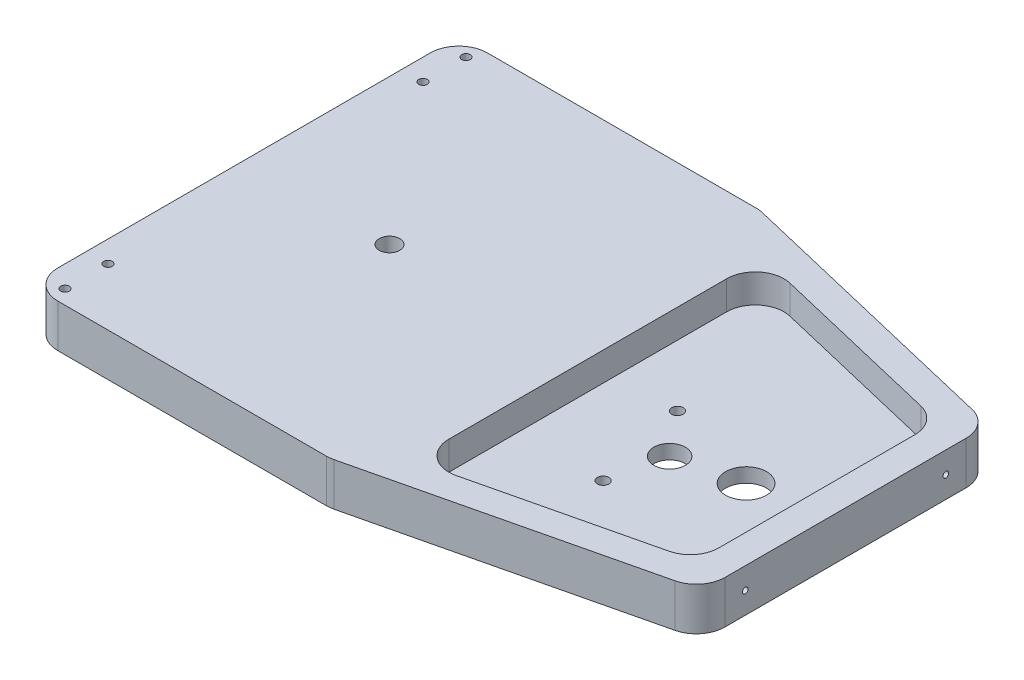
SolidWorks part; units mm, degrees
material "Carvalho"
ref_plane "Plano frontal" through (0, 0, 0) normal (0, 0, 1) x (1, 0, 0)
ref_plane "Plano superior" through (0, 0, 0) normal (0, 1, 0) x (1, 0, 0)
ref_plane "Plano direito" through (0, 0, 0) normal (1, 0, 0) x (0, 0, -1)
sketch "Esboço1" plane through (0, 0, 0) normal (0, 1, 0) x (1, 0, 0)
  line L0 (210, 50) -> (105, 75)
  line L1 (0, -75) -> (105, -75)
  line L2 (0, -75) -> (0, 75)
  line L3 (0, 75) -> (105, 75)
  line L4 (210, -50) -> (210, 50)
  line L7 (105, -75) -> (210, -50)
  line L8 (-14.8259, 0) -> (14.392, 0) construction
  line L9 (0, 21.2472) -> (0, -16.7598) construction
  circle A0 centre (50.8, 0) radius 3.5719
  circle A1 centre (175.26, 0) radius 7.14
  circle A2 centre (153.7069, -5.1317) radius 5.5
  circle A3 centre (153.7069, -5.1317) radius 4.5 construction
  circle A4 centre (7.5, -70) radius 1.5
  circle A5 centre (7.5, -55) radius 1.5
  circle A6 centre (7.5, -70) radius 1.5 construction
  circle A7 centre (7.5, -55) radius 1.5 construction
  circle A8 centre (7.5, 55) radius 1.5
  circle A9 centre (7.5, 70) radius 1.5
  point P0 (0, 0)
  dimension "D3" = 7.1437
  dimension "D5" = 14.28
  dimension "D9" = 1
  dimension "D1" = 25
  dimension "D2" = 150
  dimension "D4" = 50.8
  dimension "D6" = 210
  dimension "D7" = 175.26
  dimension "D8" = 105
extrude "Ressalto-extrusão1" add sketch "Esboço1" along normal blind 15
sketch "Esboço2" plane through (210, 0, 0) normal (1, 0, 0) x (0, 0, -1)
  line L0 (0, 15) -> (0, 0) construction
  line L1 (-50, 15) -> (50, 15) construction
  circle A0 centre (35, 7.5) radius 1
  circle A1 centre (-35, 7.5) radius 1
  point P9 (0, 7.5)
  dimension "D1" = 2
  dimension "D2" = 35
extrude "Corte-extrusão1" cut sketch "Esboço2" against normal blind 10
sketch "Esboço3" plane through (0, 15, 0) normal (0, 1, 0) x (1, 0, 0)
  line L0 (200, 42.1014) -> (200, -42.1014)
  line L1 (200, -42.1014) -> (120, -61.149)
  line L2 (120, -61.149) -> (120, 61.149)
  line L3 (120, 61.149) -> (200, 42.1014)
  line L4 (210, 50) -> (105, 75) construction
  line L5 (105, -75) -> (210, -50) construction
  line L6 (210, -50) -> (210, 50) construction
  line L7 (0, 75) -> (0, -75) construction
  line L8 (-22.821, 0) -> (224.4652, 0) construction
  dimension "D1" = 10
  dimension "D2" = 120
  dimension "D3" = 10
extrude "Corte-extrusão2" cut sketch "Esboço3" against normal blind 10
fillet "Filete1" radius 10 10 edges at (105, 7.5, 75) (0, 7.5, 75) (0, 7.5, -75) (210, 7.5, 50) (105, 7.5, -75) (210, 7.5, -50) (120, 10, 61.149) (200, 10, 42.1014) (200, 10, -42.1014) (120, 10, -61.149)
sketch "Esboço5" plane through (0, 0, 0) normal (0, -1, 0) x (1, 0, 0)
  line L0 (175.26, 0) -> (111.2499, 15.2405) construction
  line L1 (106.1421, 74.7281) -> (202.3162, 51.8295) construction
  line L2 (149.4914, 24.1246) -> (141.3847, -9.9236) construction
  circle A0 centre (149.4914, 24.1246) radius 2
  circle A1 centre (141.3847, -9.9236) radius 2
  point P2 (0, 0)
  point P5 (145.438, 7.1005)
  point P7 (175.26, 0)
  dimension "D1" = 35
extrude "Corte-extrusão4" cut sketch "Esboço5" against normal through all
